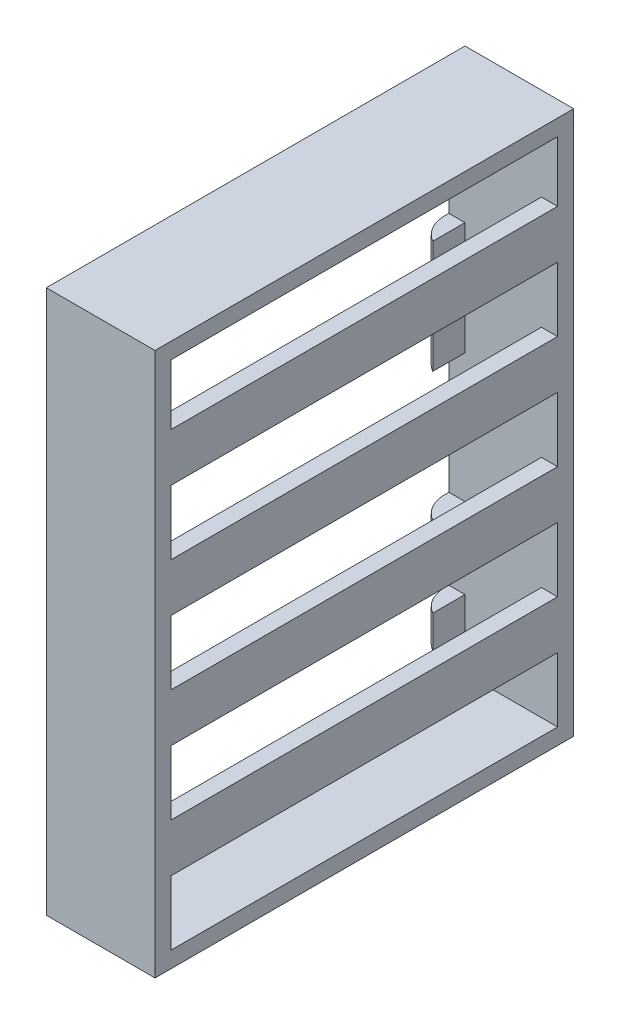
SolidWorks part; units mm, degrees
ref_plane "前视基准面" through (0, 0, 0) normal (0, 0, 1) x (1, 0, 0)
ref_plane "上视基准面" through (0, 0, 0) normal (0, 1, 0) x (1, 0, 0)
ref_plane "右视基准面" through (0, 0, 0) normal (1, 0, 0) x (0, 0, -1)
sketch "草图1" plane through (0, 0, 0) normal (0, 0, 1) x (1, 0, 0)
  line L1 (-2.7902, 8.4682) -> (10.7098, 8.4682)
  line L2 (-2.7902, 8.4682) -> (-2.7902, -59.0318)
  line L3 (-2.7902, -59.0318) -> (10.7098, -59.0318)
  line L4 (10.7098, 8.4682) -> (10.7098, -59.0318)
  dimension "D1" = 13.5
  dimension "D2" = 67.5
extrude "凸台-拉伸1" add sketch "草图1" along normal blind 52
sketch "草图2" plane through (10.7098, 0, 0) normal (1, 0, 0) x (0, 0, -1)
  line L0 (-52, 8.4682) -> (0, 8.4682) construction
  line L1 (-50, 6.4682) -> (-2, 6.4682)
  line L2 (-50, 6.4682) -> (-50, -57.0318)
  line L3 (-50, -57.0318) -> (-2, -57.0318)
  line L4 (-2, 6.4682) -> (-2, -57.0318)
  line L5 (0, -59.0318) -> (0, 8.4682) construction
  line L7 (-52, -59.0318) -> (-52, 8.4682) construction
  line L8 (-52, -59.0318) -> (0, -59.0318) construction
  dimension "D1" = 2
  dimension "D2" = 2
  dimension "D3" = 2
  dimension "D4" = 2
extrude "切除-拉伸1" cut sketch "草图2" against normal up to next
sketch "草图3" plane through (0, 0, 50) normal (0, 0, -1) x (-1, 0, 0)
  line L0 (2.7902, 6.4682) -> (-10.7098, 6.4682) construction
  line L1 (-10.7098, -1.0318) -> (-8.7098, -1.0318)
  line L2 (-10.7098, -1.0318) -> (-10.7098, -7.0318)
  line L3 (-10.7098, -7.0318) -> (-8.7098, -7.0318)
  line L4 (-8.7098, -1.0318) -> (-8.7098, -7.0318)
  line L5 (-10.7098, 6.4682) -> (-10.7098, -57.0318) construction
  line L22 (-10.7098, -15.0318) -> (-10.7098, -21.0318)
  line L23 (-10.7098, -15.0318) -> (-8.7098, -15.0318)
  line L24 (-8.7098, -15.0318) -> (-8.7098, -21.0318)
  line L25 (-10.7098, -21.0318) -> (-8.7098, -21.0318)
  line L26 (-10.7098, -29.0318) -> (-10.7098, -35.0318)
  line L27 (-10.7098, -29.0318) -> (-8.7098, -29.0318)
  line L28 (-8.7098, -29.0318) -> (-8.7098, -35.0318)
  line L29 (-10.7098, -35.0318) -> (-8.7098, -35.0318)
  line L30 (-10.7098, -43.0318) -> (-10.7098, -49.0318)
  line L31 (-10.7098, -43.0318) -> (-8.7098, -43.0318)
  line L32 (-8.7098, -43.0318) -> (-8.7098, -49.0318)
  line L33 (-10.7098, -49.0318) -> (-8.7098, -49.0318)
  point P8 (0.2902, -6.5318)
  point P12 (-9.7098, -36.5318)
  dimension "D1" = 2
  dimension "D2" = 6
  dimension "D3" = 7.5
  dimension "D4" = 4
extrude "凸台-拉伸2" add sketch "草图3" along normal up to next
sketch "草图9" plane through (0, 0, 50) normal (0, 0, -1) x (-1, 0, 0)
  line L0 (2.7902, -57.0318) -> (2.7902, 6.4682) construction
  line L1 (2.7902, 1.4682) -> (0.7902, 1.4682)
  line L2 (2.7902, 1.4682) -> (2.7902, -2.5318)
  line L3 (2.7902, -2.5318) -> (0.7902, -2.5318)
  line L4 (0.7902, 1.4682) -> (0.7902, -2.5318)
  line L5 (2.7902, 6.4682) -> (-10.7098, 6.4682) construction
  line L6 (2.7902, -8.5318) -> (2.7902, -12.5318)
  line L7 (2.7902, -8.5318) -> (0.7902, -8.5318)
  line L8 (0.7902, -8.5318) -> (0.7902, -12.5318)
  line L9 (2.7902, -12.5318) -> (0.7902, -12.5318)
  line L10 (2.7902, -18.5318) -> (2.7902, -22.5318)
  line L11 (2.7902, -18.5318) -> (0.7902, -18.5318)
  line L12 (0.7902, -18.5318) -> (0.7902, -22.5318)
  line L13 (2.7902, -22.5318) -> (0.7902, -22.5318)
  line L14 (2.7902, -28.5318) -> (2.7902, -32.5318)
  line L15 (2.7902, -28.5318) -> (0.7902, -28.5318)
  line L16 (0.7902, -28.5318) -> (0.7902, -32.5318)
  line L17 (2.7902, -32.5318) -> (0.7902, -32.5318)
  line L18 (2.7902, -38.5318) -> (2.7902, -42.5318)
  line L19 (2.7902, -38.5318) -> (0.7902, -38.5318)
  line L20 (0.7902, -38.5318) -> (0.7902, -42.5318)
  line L21 (2.7902, -42.5318) -> (0.7902, -42.5318)
  line L22 (2.7902, -48.5318) -> (2.7902, -52.5318)
  line L23 (2.7902, -48.5318) -> (0.7902, -48.5318)
  line L24 (0.7902, -48.5318) -> (0.7902, -52.5318)
  line L25 (2.7902, -52.5318) -> (0.7902, -52.5318)
  dimension "D1" = 2
  dimension "D2" = 4
  dimension "D3" = 5
  dimension "D4" = 6
extrude "凸台-拉伸3" add sketch "草图9" along normal blind 4
sketch "草图10" plane through (0, 6.4682, 0) normal (0, -1, 0) x (1, 0, 0)
  line L0 (-2.7902, 50) -> (-2.7902, 2) construction
  line L1 (-0.7902, 6) -> (-2.7902, 6)
  line L2 (-0.7902, 6) -> (-0.7902, 10)
  line L3 (-0.7902, 10) -> (-2.7902, 10)
  line L4 (-2.7902, 6) -> (-2.7902, 10)
  line L5 (-2.7902, 2) -> (10.7098, 2) construction
  line L6 (-0.7902, 15) -> (-0.7902, 19)
  line L7 (-0.7902, 15) -> (-2.7902, 15)
  line L8 (-2.7902, 15) -> (-2.7902, 19)
  line L9 (-0.7902, 19) -> (-2.7902, 19)
  line L10 (-0.7902, 24) -> (-0.7902, 28)
  line L11 (-0.7902, 24) -> (-2.7902, 24)
  line L12 (-2.7902, 24) -> (-2.7902, 28)
  line L13 (-0.7902, 28) -> (-2.7902, 28)
  line L14 (-0.7902, 33) -> (-0.7902, 37)
  line L15 (-0.7902, 33) -> (-2.7902, 33)
  line L16 (-2.7902, 33) -> (-2.7902, 37)
  line L17 (-0.7902, 37) -> (-2.7902, 37)
  line L18 (-0.7902, 42) -> (-0.7902, 46)
  line L19 (-0.7902, 42) -> (-2.7902, 42)
  line L20 (-2.7902, 42) -> (-2.7902, 46)
  line L21 (-0.7902, 46) -> (-2.7902, 46)
  dimension "D1" = 2
  dimension "D2" = 4
  dimension "D3" = 4
  dimension "D4" = 5
extrude "凸台-拉伸4" add sketch "草图10" along normal blind 4
sketch "草图11" plane through (0, -57.0318, 0) normal (0, 1, 0) x (1, 0, 0)
  line L0 (-2.7902, -2) -> (-2.7902, -50) construction
  line L1 (-2.7902, -42) -> (-0.7902, -42)
  line L2 (-2.7902, -42) -> (-2.7902, -46)
  line L3 (-2.7902, -46) -> (-0.7902, -46)
  line L4 (-0.7902, -42) -> (-0.7902, -46)
  line L5 (-2.7902, -50) -> (10.7098, -50) construction
  line L6 (-2.7902, -33) -> (-2.7902, -37)
  line L7 (-2.7902, -33) -> (-0.7902, -33)
  line L8 (-0.7902, -33) -> (-0.7902, -37)
  line L9 (-2.7902, -37) -> (-0.7902, -37)
  line L10 (-2.7902, -24) -> (-2.7902, -28)
  line L11 (-2.7902, -24) -> (-0.7902, -24)
  line L12 (-0.7902, -24) -> (-0.7902, -28)
  line L13 (-2.7902, -28) -> (-0.7902, -28)
  line L14 (-2.7902, -15) -> (-2.7902, -19)
  line L15 (-2.7902, -15) -> (-0.7902, -15)
  line L16 (-0.7902, -15) -> (-0.7902, -19)
  line L17 (-2.7902, -19) -> (-0.7902, -19)
  line L18 (-2.7902, -6) -> (-2.7902, -10)
  line L19 (-2.7902, -6) -> (-0.7902, -6)
  line L20 (-0.7902, -6) -> (-0.7902, -10)
  line L21 (-2.7902, -10) -> (-0.7902, -10)
  point P8 (-1.7902, -46)
  dimension "D1" = 2
  dimension "D2" = 4
  dimension "D3" = 4
  dimension "D4" = 5
extrude "凸台-拉伸5" add sketch "草图11" along normal blind 4
sketch "草图12" plane through (0, 0, 2) normal (0, 0, 1) x (1, 0, 0)
  line L0 (-2.7902, 6.4682) -> (-2.7902, -57.0318) construction
  line L1 (-0.7902, -2.5318) -> (-2.7902, -2.5318)
  line L2 (-0.7902, -2.5318) -> (-0.7902, 1.4682)
  line L3 (-0.7902, 1.4682) -> (-2.7902, 1.4682)
  line L4 (-2.7902, -2.5318) -> (-2.7902, 1.4682)
  line L5 (-2.7902, 6.4682) -> (10.7098, 6.4682) construction
  line L6 (-0.7902, -12.5318) -> (-0.7902, -8.5318)
  line L7 (-0.7902, -12.5318) -> (-2.7902, -12.5318)
  line L8 (-2.7902, -12.5318) -> (-2.7902, -8.5318)
  line L9 (-0.7902, -8.5318) -> (-2.7902, -8.5318)
  line L10 (-0.7902, -22.5318) -> (-0.7902, -18.5318)
  line L11 (-0.7902, -22.5318) -> (-2.7902, -22.5318)
  line L12 (-2.7902, -22.5318) -> (-2.7902, -18.5318)
  line L13 (-0.7902, -18.5318) -> (-2.7902, -18.5318)
  line L14 (-0.7902, -32.5318) -> (-0.7902, -28.5318)
  line L15 (-0.7902, -32.5318) -> (-2.7902, -32.5318)
  line L16 (-2.7902, -32.5318) -> (-2.7902, -28.5318)
  line L17 (-0.7902, -28.5318) -> (-2.7902, -28.5318)
  line L18 (-0.7902, -42.5318) -> (-0.7902, -38.5318)
  line L19 (-0.7902, -42.5318) -> (-2.7902, -42.5318)
  line L20 (-2.7902, -42.5318) -> (-2.7902, -38.5318)
  line L21 (-0.7902, -38.5318) -> (-2.7902, -38.5318)
  line L22 (-0.7902, -52.5318) -> (-0.7902, -48.5318)
  line L23 (-0.7902, -52.5318) -> (-2.7902, -52.5318)
  line L24 (-2.7902, -52.5318) -> (-2.7902, -48.5318)
  line L25 (-0.7902, -48.5318) -> (-2.7902, -48.5318)
  dimension "D1" = 4
  dimension "D2" = 2
  dimension "D3" = 5
  dimension "D4" = 6
extrude "凸台-拉伸6" add sketch "草图12" along normal blind 4
fillet "圆角1" radius 4 22 edges at (-2.7902, -50.5318, 46) (-2.7902, -53.0318, 44) (-2.7902, -40.5318, 46) (-2.7902, -30.5318, 46) (-2.7902, -53.0318, 35) (-2.7902, -53.0318, 26) (-2.7902, -53.0318, 17) (-2.7902, -50.5318, 6) (-2.7902, -53.0318, 8) (-2.7902, -40.5318, 6) (-2.7902, -20.5318, 6) (-2.7902, -30.5318, 6) (-2.7902, -10.5318, 6) (-2.7902, -0.5318, 6) (-2.7902, 2.4682, 8) (-2.7902, 2.4682, 17) (-2.7902, 2.4682, 26) (-2.7902, 2.4682, 35) (-2.7902, 2.4682, 44) (-2.7902, -0.5318, 46) (-2.7902, -10.5318, 46) (-2.7902, -20.5318, 46)
